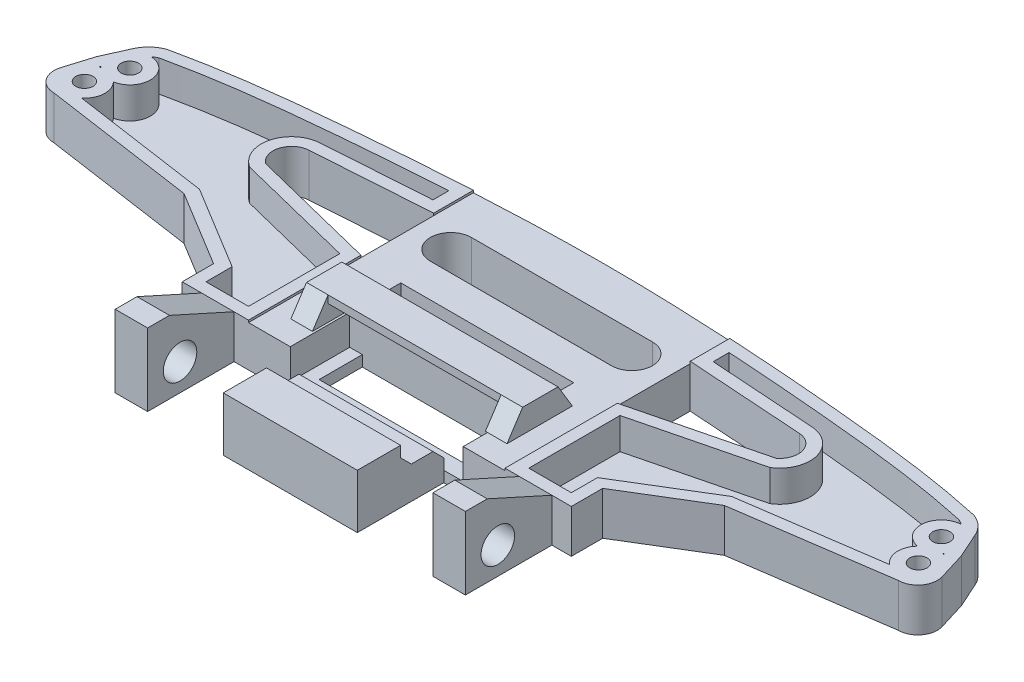
SolidWorks part; units mm, degrees
ref_plane "前视基准面" through (0, 0, 0) normal (0, 0, 1) x (1, 0, 0)
ref_plane "上视基准面" through (0, 0, 0) normal (0, 1, 0) x (1, 0, 0)
ref_plane "右视基准面" through (0, 0, 0) normal (1, 0, 0) x (0, 0, -1)
sketch "草图1" plane through (0, 0, 0) normal (0, 1, 0) x (1, 0, 0)
  line L0 (0, 20.1146) -> (0, -28.2009) construction
  line L1 (-33.9985, 0) -> (36.882, 0) construction
  line L2 (-40, 5.4973) -> (-38.955, 7.8217)
  line L3 (-24.9943, -1.4262) -> (-18, -5.6823)
  line L4 (-18, -7.9072) -> (-18, -8.5838)
  line L5 (-18, -8.5838) -> (18, -8.5838)
  line L6 (-40, 5.4973) -> (-40.7796, 2.9495)
  line L7 (-39.0526, 0.6151) -> (-24.9943, -1.4262)
  line L8 (-18, -5.6823) -> (-18, -7.9072)
  line L9 (-8.3723, 6.648) -> (8.3723, 6.648) construction
  line L10 (-8.3723, 8.551) -> (8.3723, 8.551)
  line L11 (-8.3723, 4.745) -> (8.3723, 4.745)
  line L12 (-11.8642, 12.216) -> (-11.8642, -8.5838)
  line L13 (-11.8642, 8.551) -> (-22.6968, 7.8217)
  line L14 (-23.6075, 4.745) -> (-11.8642, 1.8161)
  line L15 (23.6075, 4.745) -> (11.8642, 1.8161)
  line L16 (11.8642, 8.551) -> (22.6968, 7.8217)
  line L17 (11.8642, 12.216) -> (11.8642, -8.5838)
  line L18 (18, -5.6823) -> (18, -7.9072)
  line L19 (39.0526, 0.6151) -> (24.9943, -1.4262)
  line L20 (40, 5.4973) -> (40.7796, 2.9495)
  line L21 (18, -7.9072) -> (18, -8.5838)
  line L22 (24.9943, -1.4262) -> (18, -5.6823)
  line L23 (40, 5.4973) -> (38.955, 7.8217)
  line L24 (-16.2, -8.5838) -> (-16.2, -16.5838)
  line L25 (-16.2, -16.5838) -> (-13.2, -16.5838)
  line L26 (-13.2, -16.5838) -> (-13.2, -8.5838)
  line L27 (16.2, -8.5838) -> (16.2, -16.5838)
  line L28 (13.2, -16.5838) -> (13.2, -8.5838)
  line L29 (16.2, -16.5838) -> (13.2, -16.5838)
  line L30 (-13.2, -16.5838) -> (13.2, -16.5838)
  line L31 (-13.2, -12.5838) -> (13.2, -12.5838)
  line L32 (-6.2, -8.5838) -> (-6.2, -16.5838)
  line L33 (6.2, -8.5838) -> (6.2, -16.5838)
  arc A0 (-38.955, 7.8217) -> (-37.3062, 9.3441) centre (-36.3441, 6.648) cw
  arc A1 (-40.7796, 2.9495) -> (-39.0526, 0.6151) centre (-39.0526, 2.4211) ccw
  arc A2 (-8.3723, 8.551) -> (-8.3723, 4.745) centre (-8.3723, 6.648) ccw
  arc A3 (8.3723, 4.745) -> (8.3723, 8.551) centre (8.3723, 6.648) ccw
  arc A4 (-22.6968, 7.8217) -> (-23.6075, 4.745) centre (-22.5819, 6.1146) ccw
  arc A5 (22.6968, 7.8217) -> (23.6075, 4.745) centre (22.5819, 6.1146) cw
  arc A6 (40.7796, 2.9495) -> (39.0526, 0.6151) centre (39.0526, 2.4211) cw
  arc A7 (38.955, 7.8217) -> (37.3062, 9.3441) centre (36.3441, 6.648) ccw
  circle A8 centre (-38.5785, 2.9495) radius 0.8
  circle A9 centre (-37.5412, 6.1146) radius 0.8
  circle A10 centre (37.5412, 6.1146) radius 0.8
  circle A11 centre (38.5785, 2.9495) radius 0.8
  spline S0 degree 3 poles (-37.3062, 9.3441) (-32.2431, 10.4644) (-19.802, 11.7944) (-7.3281, 12.5738) (0, 12.5738) knots 0 0 0 0 0.414185 1 1 1 1
  spline S1 degree 3 poles (37.3062, 9.3441) (32.2431, 10.4644) (19.802, 11.7944) (7.3281, 12.5738) (0, 12.5738) knots 0 0 0 0 0.414185 1 1 1 1
  point P23 (0, 6.648)
  point P35 (0, -8.5838)
  dimension "D5" = 13.2
  dimension "D1" = 40
  dimension "D2" = 14
  dimension "D3" = 22
  dimension "D4" = 18
  dimension "D6" = 3
  dimension "D7" = 8
  dimension "D8" = 7
extrude "凸台-拉伸1" add sketch "草图1" along normal blind 4 contours S0 A0 L2 L6 A1 L7 L3 L8 L4 L5 L12 L14 A4 L13 A9 A8 | A7 S1 L17 L16 A5 L15 L5 L21 L18 L22 L19 A6 L20 L23 A10 A11 region at (-24.4846, 0, -3.1835) region at (24.4846, 0, -3.1835)
shell "抽壳1" thickness 1.1 removed face at (-26.0988, 4, -2.5511)
shell "抽壳2" thickness 1.1 removed face at (37.5412, 4, -5.3146)
extrude "凸台-拉伸2" add sketch "草图1<3>" along normal blind 3.8 contours L17 S1 S0 L12 L5 A3 L11 A2 L10 region at (0, 0, -1.0989)
sketch "草图1<3>" plane through (0, 0, 0) normal (0, 1, 0) x (1, 0, 0) same geometry as "草图1"
extrude "凸台-拉伸3" add sketch "草图1<5>" along normal blind 6.7 contours L25 L26 L5 L24 | L29 L27 L5 L28 region at (-14.7, 0, 12.5838) region at (14.7, 0, 12.5838)
sketch "草图1<5>" plane through (0, 0, 0) normal (0, 1, 0) x (1, 0, 0) same geometry as "草图1"
sketch "草图2" plane through (-16.2, 0, 0) normal (-1, 0, 0) x (0, 0, 1)
  line L0 (16.5838, 6.7) -> (16.5838, 0) construction
  line L1 (8.5838, 0) -> (16.5838, 0) construction
  line L2 (8.5838, 4) -> (14.563, 6.7)
  line L3 (8.5838, 6.7) -> (16.5838, 6.7) construction
  line L4 (14.563, 6.7) -> (8.5838, 6.7)
  line L5 (8.5838, 6.7) -> (8.5838, 4)
  circle A0 centre (13.5838, 2.5) radius 1.55
  dimension "D1" = 3
  dimension "D3" = 3.1
  dimension "D2" = 2.5
extrude "切除-拉伸1" cut sketch "草图2" against normal up to next
mirror "镜向1" about plane through (0, 0, 0) normal (1, 0, 0) of "切除-拉伸1"
extrude "凸台-拉伸4" add sketch "草图1<8>" along normal blind 5 separate body contours L33 L31 L32 L30 region at (0, 0, 14.5838)
sketch "草图1<8>" plane through (0, 0, 0) normal (0, 1, 0) x (1, 0, 0) same geometry as "草图1"
extrude "凸台-拉伸5" add sketch "草图1<9>" along normal blind 3 contours L33 L5 L32 L31 region at (0, 0, 10.5838)
sketch "草图1<9>" plane through (0, 0, 0) normal (0, 1, 0) x (1, 0, 0) same geometry as "草图1"
sketch "草图4" plane through (0, 0, 0) normal (1, 0, 0) x (0, 0, -1)
  line L0 (-5.6823, 0) -> (-8.5838, 0) construction
  line L1 (-8.5838, 4) -> (1.6414, 4)
  line L2 (-8.5838, 4) -> (-8.5838, 1)
  line L3 (-8.5838, 1) -> (1.6414, 1)
  line L4 (1.6414, 4) -> (1.6414, 1)
  dimension "D1" = 1
extrude "切除-拉伸2" cut sketch "草图4" against normal mid plane 16
sketch "草图3" plane through (0, 0, 0) normal (1, 0, 0) x (0, 0, -1)
  line L0 (-3.0838, 0.7) -> (-1.8173, 0.7)
  line L2 (0, 3.2) -> (1.0619, 0.7)
  line L3 (1.0619, 0.7) -> (0, 0.7)
  line L4 (-3.0838, 3.2) -> (-3.0838, 0.7)
  line L6 (-1.8173, 6.2) -> (-5.0838, 6.2)
  line L7 (-5.0838, 6.2) -> (-5.0838, 5.5)
  line L8 (-5.0838, 5.5) -> (-3.0838, 5.5)
  line L9 (-8.5838, 0.7) -> (1.6414, 0.7) construction
  line L11 (0, 0.7) -> (-1.8173, 0.7)
  line L12 (-3.0838, 5.5) -> (-3.0838, 3.2)
  line L13 (-1.8173, 6.2) -> (0, 3.2)
  dimension "D1" = 0.7
extrude "凸台-拉伸6" add sketch "草图3" along normal mid plane 16
chamfer "倒角2" distance 1 angle 45 2 edges at (0, 3, 8.5838) (0, 3, 12.5838)
sketch "草图5" plane through (0, 1, 0) normal (0, 1, 0) x (1, 0, 0)
  line L1 (6.8353, -7.0838) -> (-6.8353, -7.0838)
  line L2 (6.8353, -7.0838) -> (6.8353, -3.0838)
  line L3 (6.8353, -3.0838) -> (-6.8353, -3.0838)
  line L4 (-6.8353, -7.0838) -> (-6.8353, -3.0838)
  line L5 (6.8353, -7.0838) -> (-6.8353, -3.0838) construction
  line L6 (6.8353, -3.0838) -> (-6.8353, -7.0838) construction
  point P0 (0, -5.0838)
  dimension "D1" = 4
extrude "切除-拉伸3" cut sketch "草图5" against normal up to next
sketch "草图6" plane through (-8, 0, 0) normal (-1, 0, 0) x (0, 0, 1)
  line L0 (1.8173, 6.2) -> (0.4846, 4)
  line L1 (-0.6151, 4) -> (1.4262, 4) construction
  line L2 (0.3635, 3.8) -> (1.8173, 6.2) construction
  line L3 (0.4846, 4) -> (6.5337, 4)
  line L4 (5.6823, 4) -> (8.5838, 4) construction
  line L5 (6.5337, 4) -> (5.0838, 6.2)
  line L6 (5.0838, 6.2) -> (1.8173, 6.2)
extrude "凸台-拉伸7" add sketch "草图6" along normal blind 2
sketch "草图7" plane through (8, 0, 0) normal (1, 0, 0) x (0, 0, -1)
  line L0 (-1.8173, 6.2) -> (-5.0838, 6.2)
  line L1 (-5.0838, 6.2) -> (-6.5337, 4)
  line L2 (-6.5337, 4) -> (-0.4846, 4)
  line L3 (-0.4846, 4) -> (-1.8173, 6.2)
extrude "凸台-拉伸8" add sketch "草图7" along normal blind 2
